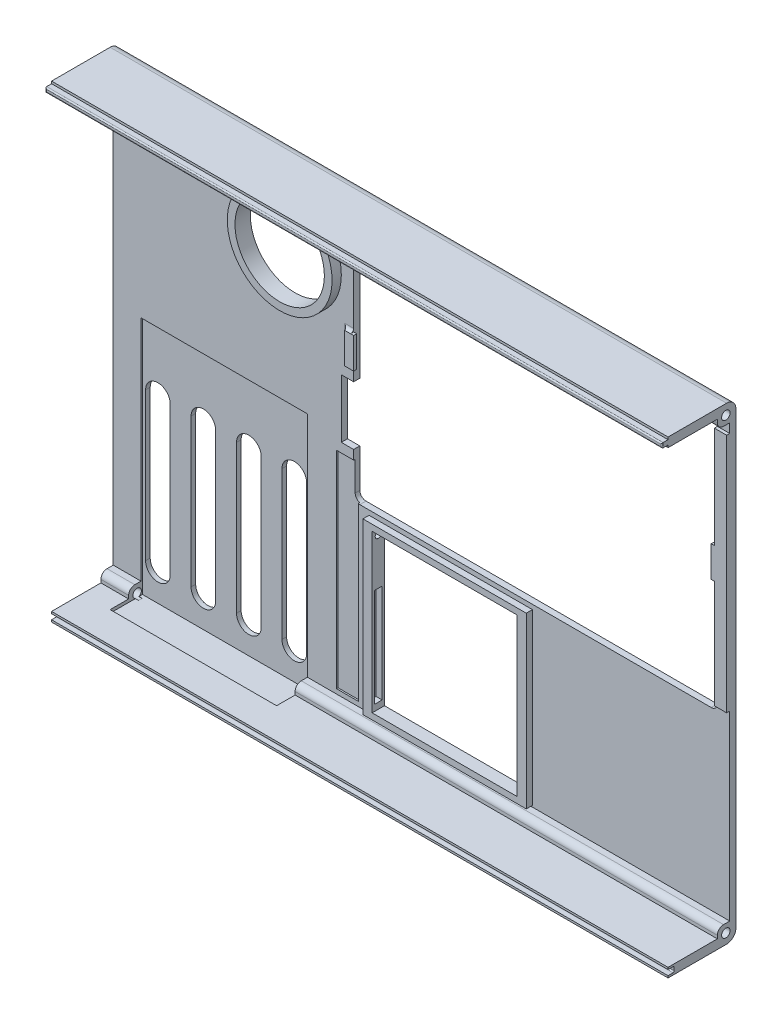
SolidWorks part; units mm, degrees
ref_plane "Front Plane" through (0, 0, 0) normal (0, 0, 1) x (1, 0, 0)
ref_plane "Top Plane" through (0, 0, 0) normal (0, 1, 0) x (1, 0, 0)
ref_plane "Right Plane" through (0, 0, 0) normal (1, 0, 0) x (0, 0, -1)
sketch "Sketch1" plane through (0, 0, 0) normal (0, 0, 1) x (1, 0, 0)
  line L1 (105, -90.3987) -> (-95, -90.3987)
  line L2 (105, -90.3987) -> (105, 61.6013)
  line L3 (105, 61.6013) -> (-95, 61.6013)
  line L4 (-95, -90.3987) -> (-95, 61.6013)
  line L5 (105, -90.3987) -> (-95, 61.6013) construction
  line L6 (105, 61.6013) -> (-95, -90.3987) construction
  point P0 (5, -14.3987)
  dimension "D1" = 200
  dimension "D2" = 152
extrude "body" add sketch "Sketch1" along normal blind 2
sketch "Sketch3" plane through (0, 0, 0) normal (0, 0, -1) x (-1, 0, 0)
  line L0 (95, -54.3987) -> (-105, -54.3987) construction
  line L1 (95, 61.6013) -> (95, -90.3987) construction
  line L2 (-105, -90.3987) -> (-105, 61.6013) construction
  line L3 (66.25, -78.3987) -> (66.25, -30.3987) construction
  line L4 (62.25, -78.3987) -> (62.25, -30.3987)
  line L5 (70.25, -78.3987) -> (70.25, -30.3987)
  line L6 (95, -30.3987) -> (-105, -30.3987) construction
  line L7 (81, -78.3987) -> (81, -30.3987) construction
  line L8 (95, -78.3987) -> (-105, -78.3987) construction
  line L9 (77, -78.3987) -> (77, -30.3987)
  line L10 (85, -78.3987) -> (85, -30.3987)
  line L11 (51.5, -78.3987) -> (51.5, -30.3987) construction
  line L12 (47.5, -78.3987) -> (47.5, -30.3987)
  line L13 (55.5, -78.3987) -> (55.5, -30.3987)
  line L14 (36.75, -78.3987) -> (36.75, -30.3987) construction
  line L15 (32.75, -78.3987) -> (32.75, -30.3987)
  line L16 (40.75, -78.3987) -> (40.75, -30.3987)
  line L17 (95, -90.3987) -> (95, 61.6013) construction
  line L18 (-105, 61.6013) -> (95, 61.6013) construction
  line L19 (95, -90.3987) -> (-105, -90.3987) construction
  line L20 (-105, -90.3987) -> (-105, 61.6013) construction
  circle A0 centre (38, 34.1013) radius 14.5
  arc A1 (62.25, -78.3987) -> (70.25, -78.3987) centre (66.25, -78.3987) ccw
  arc A2 (70.25, -30.3987) -> (62.25, -30.3987) centre (66.25, -30.3987) ccw
  arc A3 (77, -78.3987) -> (85, -78.3987) centre (81, -78.3987) ccw
  arc A4 (85, -30.3987) -> (77, -30.3987) centre (81, -30.3987) ccw
  arc A5 (47.5, -78.3987) -> (55.5, -78.3987) centre (51.5, -78.3987) ccw
  arc A6 (55.5, -30.3987) -> (47.5, -30.3987) centre (51.5, -30.3987) ccw
  arc A7 (32.75, -78.3987) -> (40.75, -78.3987) centre (36.75, -78.3987) ccw
  arc A8 (40.75, -30.3987) -> (32.75, -30.3987) centre (36.75, -30.3987) ccw
  point P10 (66.25, -54.3987)
  point P21 (81, -54.3987)
  point P27 (51.5, -54.3987)
  point P34 (36.75, -54.3987)
  dimension "D1" = 29
  dimension "D2" = 27.5
  dimension "D3" = 57
  dimension "D4" = 10
  dimension "D5" = 12
  dimension "D6" = 24
  dimension "D7" = 6.75
  dimension "D8" = 8
  dimension "D9" = 8
  dimension "D10" = 8
  dimension "D11" = 8
  dimension "D12" = 6.75
  dimension "D13" = 52.25
  dimension "D14" = 6.75
extrude "fan_exhaust_grill" cut sketch "Sketch3" against normal through all
sketch "Sketch12" plane through (0, 0, 2) normal (0, 0, 1) x (1, 0, 0)
  line L0 (-95, -90.3987) -> (-95, 61.6013) construction
  line L1 (105, -90.3987) -> (-95, -90.3987)
  line L2 (105, -90.3987) -> (105, -84.3987)
  line L3 (105, -84.3987) -> (-95, -84.3987)
  line L4 (-95, -90.3987) -> (-95, -84.3987)
  line L6 (105, 61.6013) -> (-95, 61.6013)
  line L7 (105, 61.6013) -> (105, 55.6013)
  line L8 (105, 55.6013) -> (-95, 55.6013)
  line L9 (-95, 61.6013) -> (-95, 55.6013)
  dimension "D1" = 6
  dimension "D2" = 6
extrude "side_walls" add sketch "Sketch12" along normal blind 20
sketch "Sketch14" plane through (105, 0, 0) normal (1, 0, 0) x (0, 0, -1)
  line L0 (-22, -90.3987) -> (0, -90.3987) construction
  line L1 (0, -90.3987) -> (0, 61.6013) construction
  line L2 (-22, 61.6013) -> (0, 61.6013) construction
  circle A0 centre (-3.25, -87.1487) radius 1.375
  circle A1 centre (-3.25, 58.3513) radius 1.375
  dimension "D1" = 2.75
  dimension "D2" = 2.75
  dimension "D3" = 3.25
  dimension "D4" = 3.25
  dimension "D5" = 3.25
  dimension "D6" = 3.25
  dimension "D7" = 145.5
extrude "mount_holes_l" cut sketch "Sketch14" against normal blind 10 and the other way through all
sketch "Sketch16" plane through (-95, 0, 0) normal (-1, 0, 0) x (0, 0, 1)
  line L0 (0, -90.3987) -> (0, 61.6013) construction
  line L2 (22, 61.6013) -> (0, 61.6013) construction
  line L3 (22, -90.3987) -> (0, -90.3987) construction
  circle A0 centre (3.25, -87.1487) radius 1.375
  circle A1 centre (3.25, 58.3513) radius 1.375
  dimension "D1" = 2.75
  dimension "D4" = 2.75
  dimension "D2" = 3.25
  dimension "D3" = 3.25
  dimension "D5" = 3.25
  dimension "D6" = 3.25
extrude "mount_holes_r" cut sketch "Sketch16" against normal blind 10
sketch "Sketch18" plane through (105, 0, 0) normal (1, 0, 0) x (0, 0, -1)
  line L1 (-22, -84.3987) -> (-6, -84.3987)
  line L2 (-22, -84.3987) -> (-22, -87.3987)
  line L3 (-22, -87.3987) -> (-6, -87.3987)
  line L4 (-6, -84.3987) -> (-6, -87.3987)
  line L5 (-22, 55.6013) -> (-6, 55.6013)
  line L6 (-22, 55.6013) -> (-22, 58.6013)
  line L7 (-22, 58.6013) -> (-6, 58.6013)
  line L8 (-6, 55.6013) -> (-6, 58.6013)
  dimension "D1" = 3
  dimension "D2" = 16
  dimension "D3" = 3
  dimension "D4" = 16
extrude "wall_reduce" cut sketch "Sketch18" against normal through all
sketch "Sketch19" plane through (0, 0, 22) normal (0, 0, 1) x (1, 0, 0)
  line L0 (-95, -90.3987) -> (-95, 61.6013) construction
  line L1 (-95, -89.7487) -> (105, -89.7487)
  line L2 (-95, -89.7487) -> (-95, -88.0487)
  line L3 (-95, -88.0487) -> (105, -88.0487)
  line L4 (105, -89.7487) -> (105, -88.0487)
  line L5 (105, -90.3987) -> (105, 61.6013) construction
  line L6 (-95, -90.3987) -> (105, -90.3987) construction
  line L7 (-95, -87.3987) -> (105, -87.3987) construction
  dimension "D1" = 0.65
  dimension "D2" = 1.7
  dimension "D3" = 0.65
extrude "groove" cut sketch "Sketch19" against normal blind 2
sketch "Sketch20" plane through (0, 0, 22) normal (0, 0, 1) x (1, 0, 0)
  line L0 (-95, -90.3987) -> (-95, 61.6013) construction
  line L1 (-95, 59.3513) -> (105, 59.3513)
  line L2 (-95, 59.3513) -> (-95, 60.8513)
  line L3 (-95, 60.8513) -> (105, 60.8513)
  line L4 (105, 59.3513) -> (105, 60.8513)
  line L5 (105, -90.3987) -> (105, 61.6013) construction
  line L6 (105, 61.6013) -> (-95, 61.6013) construction
  dimension "D1" = 0.75
  dimension "D2" = 1.5
extrude "notch" add sketch "Sketch20" along normal blind 2
sketch "Sketch21" plane through (0, 0, 2) normal (0, 0, 1) x (1, 0, 0)
  line L0 (105, -90.3987) -> (105, 61.6013) construction
  line L1 (101, -27.3987) -> (-17, -27.3987)
  line L2 (101, -27.3987) -> (101, 55.1013)
  line L3 (101, 55.1013) -> (-17, 55.1013)
  line L4 (-17, -27.3987) -> (-17, 55.1013)
  line L5 (105, 61.6013) -> (-95, 61.6013) construction
  dimension "D1" = 118
  dimension "D2" = 82.5
  dimension "D3" = 4
  dimension "D4" = 6.5
extrude "batt_cut" cut sketch "Sketch21" against normal through all
fillet "Fillet1" radius 3 2 edges at (5, -90.3987, 0) (5, 61.6013, 0)
fillet "Fillet2" radius 2 2 edges at (5, -84.3987, 6) (5, 55.6013, 6)
fillet "Fillet3" radius 0.4 6 edges at (5, 60.8513, 24) (105, 60.1013, 24) (5, 59.3513, 24) (-95, 60.1013, 24) (5, -89.7487, 20) (5, -88.0487, 20)
fillet "Fillet4" radius 2 4 edges at (-17, -27.3987, 1) (101, -27.3987, 1) (101, 55.1013, 1) (-17, 55.1013, 1)
sketch "Sketch22" plane through (0, 0, 2) normal (0, 0, 1) x (1, 0, 0)
  circle A0 centre (-38, 34.1013) radius 14.5
  circle A1 centre (-38, 34.1013) radius 17
  dimension "D1" = 29
  dimension "D2" = 34
extrude "fan_hole_supp" add sketch "Sketch22" along normal blind 3
sketch "Sketch23" plane through (0, 0, 2) normal (0, 0, 1) x (1, 0, 0)
  line L0 (105, -90.3987) -> (105, 61.6013) construction
  line L1 (105, 52.6013) -> (101, 52.6013)
  line L2 (105, 52.6013) -> (105, -25.3987)
  line L3 (105, -25.3987) -> (101, -25.3987)
  line L4 (101, 52.6013) -> (101, -25.3987)
  arc A0 (99, -27.3987) -> (101, -25.3987) centre (99, -25.3987) ccw construction
  dimension "D1" = 78
  dimension "D2" = 4
extrude "batt_cut_supp" add sketch "Sketch23" along normal blind 1
sketch "Sketch24" plane through (0, 0, 2) normal (0, 0, 1) x (1, 0, 0)
  line L0 (-95, -90.3987) -> (-95, 61.6013) construction
  line L1 (-86, -10.3987) -> (-32, -10.3987)
  line L2 (-86, -10.3987) -> (-86, -88.3987)
  line L3 (-86, -88.3987) -> (-32, -88.3987)
  line L4 (-32, -10.3987) -> (-32, -88.3987)
  line L5 (-95, -90.3987) -> (105, -90.3987) construction
  line L7 (-22.5, -15.8987) -> (-15.5, -15.8987)
  line L8 (-22.5, -15.8987) -> (-22.5, -82.8987)
  line L9 (-22.5, -82.8987) -> (-15.5, -82.8987)
  line L10 (-15.5, -15.8987) -> (-15.5, -82.8987)
  dimension "D1" = 9
  dimension "D2" = 2
  dimension "D3" = 54
  dimension "D4" = 78
  dimension "D5" = 9.5
  dimension "D6" = 7
  dimension "D7" = 67
  dimension "D8" = 5.5
  dimension "D9" = 5.5
extrude "Cut-Extrude1" cut sketch "Sketch24" against normal blind 10.5 from offset 10
sketch "Sketch25" plane through (0, 0, 2) normal (0, 0, 1) x (1, 0, 0)
  line L7 (-17, 53.1013) -> (-17, -15.8987) construction
  line L8 (-17, 6.1013) -> (-21, 6.1013)
  line L9 (-17, 6.1013) -> (-17, -12.8987)
  line L10 (-17, -12.8987) -> (-21, -12.8987)
  line L11 (-21, 6.1013) -> (-21, -12.8987)
  line L12 (-15, -27.3987) -> (99, -27.3987) construction
  dimension "D1" = 14.5
  dimension "D2" = 19
  dimension "D3" = 4
extrude "Cut-Extrude2" cut sketch "Sketch25" against normal through all
sketch "Sketch26" plane through (0, 0, 2) normal (0, 0, 1) x (1, 0, 0)
  line L0 (-17, 53.1013) -> (-17, 6.1013) construction
  line L1 (-17, 20.1013) -> (-19, 20.1013)
  line L2 (-17, 20.1013) -> (-17, 10.1013)
  line L3 (-17, 10.1013) -> (-19, 10.1013)
  line L4 (-19, 20.1013) -> (-19, 10.1013)
  line L10 (99, 55.1013) -> (-15, 55.1013) construction
  dimension "D4" = 2
  dimension "D5" = 10
  dimension "D6" = 35
extrude "Boss-Extrude1" add sketch "Sketch26" along normal blind 1
sketch "Sketch27" plane through (-17, 0, 0) normal (1, 0, 0) x (0, 0, -1)
  line L0 (-3, 10.1013) -> (-3, 20.1013) construction
  line L1 (-3, 20.1013) -> (-2, 20.1013)
  line L2 (-3, 20.1013) -> (-3, 10.1013)
  line L3 (-3, 10.1013) -> (-2, 10.1013)
  line L4 (-2, 20.1013) -> (-2, 10.1013)
  line L5 (-3, 20.1013) -> (-2, 20.1013) construction
extrude "Boss-Extrude2" add sketch "Sketch27" along normal blind 1
sketch "Sketch28" plane through (101, 0, 0) normal (-1, 0, 0) x (0, 0, 1)
  line L0 (0, -25.3987) -> (0, 53.1013) construction
  line L1 (2, 9.6013) -> (3, 9.6013)
  line L2 (2, 9.6013) -> (2, 19.6013)
  line L3 (2, 19.6013) -> (3, 19.6013)
  line L4 (3, 9.6013) -> (3, 19.6013)
  line L5 (3, 52.6013) -> (2, 52.6013) construction
  dimension "D1" = 1
  dimension "D2" = 2
  dimension "D3" = 10
  dimension "D4" = 33
extrude "Boss-Extrude3" add sketch "Sketch28" along normal blind 1
fillet "Fillet5" radius 1 3 edges at (-18, 20.1013, 2) (-18, 10.1013, 2) (-19, 15.1013, 2)
sketch "Sketch29" plane through (0, 0, 2) normal (0, 0, 1) x (1, 0, 0)
  line L1 (-9, -30.8987) -> (38, -30.8987)
  line L2 (-9, -30.8987) -> (-9, -81.8987)
  line L3 (-9, -81.8987) -> (38, -81.8987)
  line L4 (38, -30.8987) -> (38, -81.8987)
  line L5 (105, -90.3987) -> (105, 61.6013) construction
  line L7 (-95, -90.3987) -> (105, -90.3987) construction
  dimension "D1" = 67
  dimension "D2" = 47
  dimension "D3" = 51
  dimension "D4" = 8.5
extrude "stand_cut" cut sketch "Sketch29" against normal through all
sketch "Sketch30" plane through (0, 0, 2) normal (0, 0, 1) x (1, 0, 0)
  line L0 (-9, -81.8987) -> (38, -30.8987) construction
  line L1 (38, -30.8987) -> (-9, -30.8987) construction
  line L2 (38, -81.8987) -> (38, -30.8987) construction
  line L3 (-9, -30.8987) -> (38, -81.8987) construction
  line L5 (41, -83.8987) -> (-12, -83.8987)
  line L6 (41, -83.8987) -> (41, -28.8987)
  line L7 (41, -28.8987) -> (-12, -28.8987)
  line L8 (-12, -83.8987) -> (-12, -28.8987)
  line L9 (41, -83.8987) -> (-12, -28.8987) construction
  line L10 (41, -28.8987) -> (-12, -83.8987) construction
  line L11 (38, -81.8987) -> (-9, -81.8987)
  line L12 (38, -81.8987) -> (38, -30.8987)
  line L13 (38, -30.8987) -> (-9, -30.8987)
  line L14 (-9, -81.8987) -> (-9, -30.8987)
  line L15 (38, -81.8987) -> (-9, -30.8987) construction
  line L16 (38, -30.8987) -> (-9, -81.8987) construction
  point P11 (14.5, -56.3987)
  point P16 (14.5, -56.3987)
  dimension "D1" = 3
  dimension "D2" = 2
extrude "stand_extra_support" add sketch "Sketch30" along normal blind 2
sketch "Sketch31" plane through (-9, 0, 0) normal (1, 0, 0) x (0, 0, -1)
  line L0 (-2, -28.813) -> (-2, -81.8987) construction
  line L1 (0, -81.8987) -> (-4, -81.8987) construction
  line L2 (0, -30.8987) -> (0, -81.8987) construction
  line L3 (-0.75, -79.8987) -> (-3.25, -79.8987)
  line L4 (-0.75, -79.8987) -> (-0.75, -47.8987)
  line L5 (-0.75, -47.8987) -> (-3.25, -47.8987)
  line L6 (-3.25, -79.8987) -> (-3.25, -47.8987)
  line L7 (-0.75, -79.8987) -> (-3.25, -47.8987) construction
  line L8 (-0.75, -47.8987) -> (-3.25, -79.8987) construction
  line L9 (0, -30.8987) -> (-4, -30.8987) construction
  circle A0 centre (-2, -32.8987) radius 1
  point P4 (-2, -63.8987)
  dimension "D6" = 2
  dimension "D1" = 2
  dimension "D2" = 32
  dimension "D3" = 2.5
  dimension "D4" = 0.75
  dimension "D5" = 2
extrude "stand_right_groove" cut sketch "Sketch31" against normal blind 2
sketch "Sketch32" plane through (38, 0, 0) normal (-1, 0, 0) x (0, 0, 1)
  line L0 (2, -81.8987) -> (2, -30.8421) construction
  line L1 (0, -81.8987) -> (4, -81.8987) construction
  line L2 (0, -30.8987) -> (4, -30.8987) construction
  line L3 (3.25, -47.8987) -> (0.75, -47.8987)
  line L4 (3.25, -47.8987) -> (3.25, -79.8987)
  line L5 (3.25, -79.8987) -> (0.75, -79.8987)
  line L6 (0.75, -47.8987) -> (0.75, -79.8987)
  line L7 (3.25, -47.8987) -> (0.75, -79.8987) construction
  line L8 (3.25, -79.8987) -> (0.75, -47.8987) construction
  circle A0 centre (2, -32.8987) radius 1
  point P4 (2, -63.8987)
  dimension "D5" = 2
  dimension "D1" = 2.5
  dimension "D2" = 32
  dimension "D3" = 2
  dimension "D4" = 2
extrude "stand_left_groove" cut sketch "Sketch32" against normal blind 2
